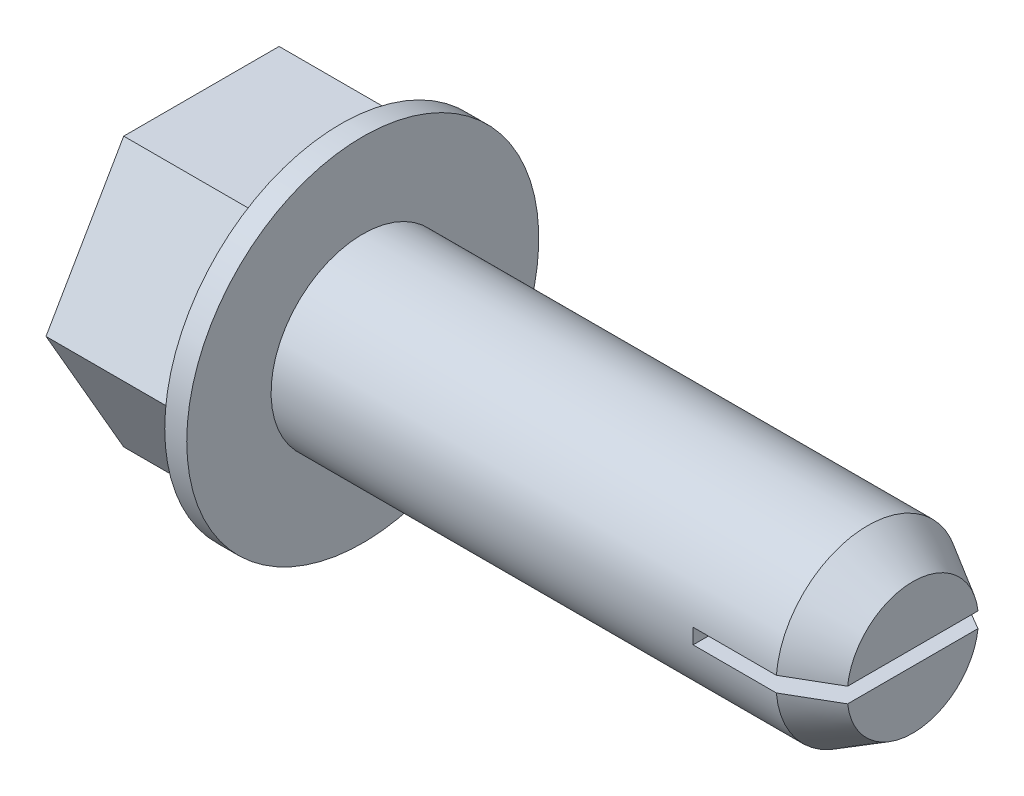
SolidWorks part; units mm, degrees
ref_plane "Front" through (0, 0, 0) normal (0, 0, 1) x (1, 0, 0)
ref_plane "Top" through (0, 0, 0) normal (0, 1, 0) x (1, 0, 0)
ref_plane "Right" through (0, 0, 0) normal (1, 0, 0) x (0, 0, -1)
ref_plane "Plane1" through (0, 0, 0) normal (0, 0, -1) x (-1, 0, 0)
sketch "Sketch1" plane through (0, 0, 0) normal (0, 0, -1) x (-1, 0, 0)
  line L0 (0, 6.096) -> (0, 0)
  line L1 (0, 0) -> (0.762, 0)
  line L2 (0.762, 0) -> (0.762, 6.096)
  line L3 (0.762, 6.096) -> (0, 6.096)
  line L4 (0, 0) -> (0.762, 0) construction
revolve "Revolve1" add sketch "Sketch1" angle 360 about L4 reverse direction yes
sketch "Sketch2" plane through (0, 0, 0) normal (1, 0, 0) x (0, 0, -1)
  circle A0 centre (0, 0) radius 3.175
extrude "Boss-Extrude1" add sketch "Sketch2" along normal blind 19.05
sketch "Sketch3" plane through (19.05, 0, 0) normal (1, 0, 0) x (0, 0, -1)
  line L0 (-3.164, -0.2646) -> (3.164, -0.2646)
  arc A0 (3.164, -0.2646) -> (-3.164, -0.2646) centre (0, 0) ccw
extrude "Cut-Extrude1" cut sketch "Sketch3" against normal blind 4.445
sketch "Sketch4" plane through (14.605, 0, 0) normal (1, 0, 0) x (0, 0, -1)
  line L0 (3.164, 0.2646) -> (-3.164, 0.2646)
  arc A0 (-3.164, 0.2646) -> (3.164, 0.2646) centre (0, 0) cw
extrude "Boss-Extrude2" add sketch "Sketch4" along normal blind 4.445
sketch "Sketch5" plane through (-0.762, 0, 0) normal (-1, 0, 0) x (0, 0, 1)
  line L0 (-2.691, -4.6609) -> (-5.3819, 0)
  line L1 (-5.3819, 0) -> (-2.691, 4.6609)
  line L2 (-2.691, 4.6609) -> (2.691, 4.6609)
  line L3 (2.691, 4.6609) -> (5.3819, 0)
  line L4 (5.3819, 0) -> (2.691, -4.6609)
  line L5 (2.691, -4.6609) -> (-2.691, -4.6609)
extrude "Boss-Extrude3" add sketch "Sketch5" along normal blind 4.826
hole_wizard "M6.5 Clearance Hole1" positions "Sketch7" profile "Sketch6" hole size "M6.5" standard "ANSI Metric"
sketch "Sketch7" plane through (-5.588, 0, 0) normal (-1, 0, 0) x (0, 0, 1)
  point P0 (0, 0)
sketch "Sketch6" plane through (-5.588, 0, 0) normal (0, 1, 0) x (0, 0, 1)
  line L0 (0, 0) -> (0, 0.9652)
  line L1 (0, 0.9652) -> (3.7287, 0.9652)
  line L2 (3.7287, 0.9652) -> (3.7287, 0)
  line L5 (3.7287, 0) -> (0, 0)
  line L10 (0, 0.9652) -> (-3.7287, 0.9652) construction
  line L11 (0, -6.35) -> (0, 107.95) construction
  dimension "Hole Dia." = 7.4574
  dimension "Hole Depth" = 0.9652
  dimension "Drill Angle" = 180
chamfer "Chamfer1" distance 0.9017 angle 60 2 edges at (19.05, 3.175, 0) (19.05, -3.175, 0) first distance on face at (19.05, 1.7198, 0) first distance on face at (19.05, -1.7198, 0)
